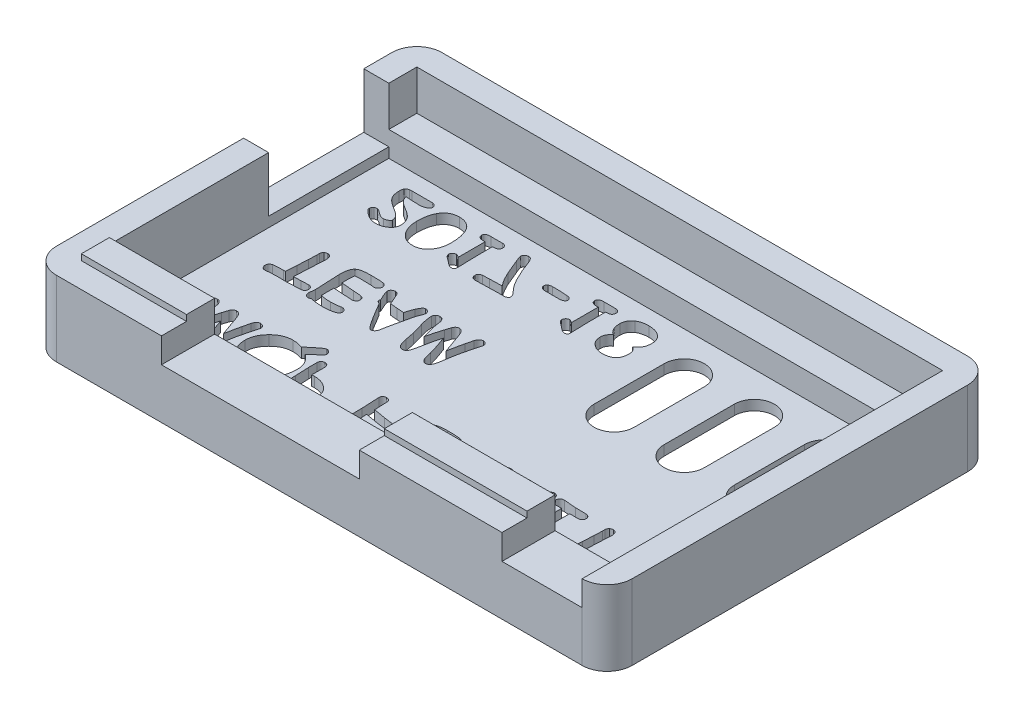
SolidWorks part; units mm, degrees
ref_plane "Front" through (0, 0, 0) normal (0, 0, 1) x (1, 0, 0)
ref_plane "Top" through (0, 0, 0) normal (0, 1, 0) x (1, 0, 0)
ref_plane "Right" through (0, 0, 0) normal (1, 0, 0) x (0, 0, -1)
sketch "Sketch1" plane through (0, 0, 0) normal (0, 1, 0) x (1, 0, 0)
  line L0 (0, 0) -> (0, 38.5)
  line L1 (0, 38.5) -> (57.5, 38.5)
  line L2 (57.5, 38.5) -> (57.5, 0)
  line L3 (57.5, 0) -> (0, 0)
  line L4 (2.5, 36) -> (2.5, 2.5)
  line L5 (2.5, 2.5) -> (55, 2.5)
  line L6 (55, 2.5) -> (55, 36)
  line L7 (55, 36) -> (2.5, 36)
  dimension "D1" = 38.5
  dimension "D2" = 57.5
  dimension "D3" = 2.5
  dimension "D4" = 2.5
  dimension "D5" = 52.5
  dimension "D6" = 33.5
extrude "Boss-Extrude1" add sketch "Sketch1" along normal blind 9
sketch "Sketch2" plane through (0, 0, 0) normal (0, 1, 0) x (1, 0, 0)
  line L1 (55, 2.5) -> (2.5, 2.5)
  line L2 (55, 2.5) -> (55, 36)
  line L3 (55, 36) -> (2.5, 36)
  line L4 (2.5, 2.5) -> (2.5, 36)
extrude "Boss-Extrude2" add sketch "Sketch2" along normal blind 2.5
sketch "Sketch3" plane through (0, 2.5, 0) normal (0, 1, 0) x (1, 0, 0)
  line L0 (2.5, 36) -> (2.5, 2.5) construction
  line L1 (55, 2.5) -> (2.5, 2.5)
  line L2 (55, 2.5) -> (55, 5.3)
  line L3 (55, 5.3) -> (2.5, 5.3)
  line L4 (2.5, 2.5) -> (2.5, 5.3)
  dimension "D1" = 2.8
extrude "Boss-Extrude3" add sketch "Sketch3" along normal blind 7.1
sketch "Sketch4" plane through (0, 0, -5.3) normal (0, 0, -1) x (-1, 0, 0)
  line L0 (-2.5, 9.6) -> (-55, 9.6) construction
  line L1 (-55, 9.6) -> (-47, 9.6)
  line L2 (-55, 9.6) -> (-55, 6.5)
  line L3 (-55, 6.5) -> (-47, 6.5)
  line L4 (-47, 9.6) -> (-47, 6.5)
  line L6 (-32.75, 9.6) -> (-13, 9.6)
  line L7 (-32.75, 9.6) -> (-32.75, 6.5)
  line L8 (-32.75, 6.5) -> (-13, 6.5)
  line L9 (-13, 9.6) -> (-13, 6.5)
  line L10 (-22.875, 9.6) -> (-22.875, 6.5) construction
  dimension "D1" = 3.1
  dimension "D2" = 3.1
  dimension "D3" = 19.75
  dimension "D4" = 8
  dimension "D5" = 14.25
sketch "Sketch5" plane through (0, 2.5, 0) normal (0, 1, 0) x (1, 0, 0)
  line L0 (55, 5.3) -> (55, 36) construction
  line L1 (2.5, 36) -> (55, 36)
  line L2 (2.5, 36) -> (2.5, 33.2)
  line L3 (2.5, 33.2) -> (55, 33.2)
  line L4 (55, 36) -> (55, 33.2)
  dimension "D1" = 2.8
extrude "Boss-Extrude4" add sketch "Sketch5" along normal blind 2.5
extrude "Cut-Extrude1" cut sketch "Sketch4" against normal up to surface (5.3 mm away) up to face at (28.75, 4.5, 0)
sketch "Sketch7" plane through (0, 0, 0) normal (-1, 0, 0) x (0, 0, 1)
  line L0 (-31.2, 9) -> (-31.2, 6) construction
  line L1 (-38.5, 9) -> (-36, 9) construction
  line L2 (-38.5, 9) -> (-38.5, 3.5) construction
  line L3 (-38.5, 3.5) -> (-36, 3.5) construction
  line L4 (-36, 9) -> (-36, 3.5) construction
  line L5 (-36, 9) -> (-33.2, 9) construction
  line L6 (-36, 9) -> (-36, 3.5) construction
  line L7 (-36, 3.5) -> (-33.2, 3.5) construction
  line L8 (-33.2, 9) -> (-33.2, 3.5)
  line L9 (-33.2, 9) -> (-21.2, 9)
  line L10 (-33.2, 9) -> (-33.2, 3.5)
  line L11 (-33.2, 3.5) -> (-21.2, 3.5)
  line L12 (-21.2, 9) -> (-21.2, 3.5)
  line L13 (-31.2, 6) -> (-23.2, 6) construction
  line L14 (-23.2, 6) -> (-23.2, 9) construction
  line M9 (0, 9) -> (-38.5, 9)
  dimension "D1" = 2.5
  dimension "D2" = 2.8
  dimension "D3" = 12
  dimension "D4" = 5.5
  dimension "D5" = 8
  dimension "D6" = 3
  dimension "D7" = 4.8
extrude "Cut-Extrude2" cut sketch "Sketch7" against normal up to surface (2.5 mm away) contours L12 L8 L11 M9 region at (0, 6.25, -27.2) up to face at (2.5, 5.5, -24.8333)
sketch "Sketch8" plane through (0, 2.5, 0) normal (0, 1, 0) x (1, 0, 0)
  line L3 (2.5, 5.3) -> (55, 5.3) construction
  line L4 (2.5, 5.3) -> (2.5, 33.2) construction
  line L5 (2.5, 33.2) -> (55, 33.2) construction
  line L6 (55, 5.3) -> (55, 33.2) construction
sketch "Sketch9" plane through (0, 0, 0) normal (0, -1, 0) x (1, 0, 0)
  line L0 (5.5, -12.3) -> (5.5, -5.3) construction
  line L1 (2.5, -5.3) -> (55, -5.3) construction
  line L2 (5.5, -12.3) -> (2.5, -12.3) construction
  line L3 (2.5, -5.3) -> (2.5, -33.2) construction
  line L4 (31, -33.2) -> (31, -18.2) construction
  line L5 (2.5, -33.2) -> (55, -33.2) construction
  line L6 (31, -18.2) -> (55, -18.2) construction
  line L7 (55, -5.3) -> (55, -33.2) construction
  line L8 (43, -18.2) -> (43, -33.2) construction
  line L9 (43, -22.2) -> (43, -29.2) construction
  line L10 (45, -22.2) -> (45, -29.2)
  line L11 (41, -22.2) -> (41, -29.2)
  line L12 (50, -22.2) -> (50, -29.2) construction
  line L13 (52, -22.2) -> (52, -29.2)
  line L14 (48, -22.2) -> (48, -29.2)
  line L15 (36, -22.2) -> (36, -29.2) construction
  line L16 (38, -22.2) -> (38, -29.2)
  line L17 (34, -22.2) -> (34, -29.2)
  arc A0 (45, -22.2) -> (41, -22.2) centre (43, -22.2) ccw
  arc A1 (41, -29.2) -> (45, -29.2) centre (43, -29.2) ccw
  arc A2 (52, -22.2) -> (48, -22.2) centre (50, -22.2) ccw
  arc A3 (48, -29.2) -> (52, -29.2) centre (50, -29.2) ccw
  arc A4 (38, -22.2) -> (34, -22.2) centre (36, -22.2) ccw
  arc A5 (34, -29.2) -> (38, -29.2) centre (36, -29.2) ccw
  text T0 "MQP HERMIT\r\nTEAM\r\n2017-18" font "Comic Sans MS" height in points 18
  point P18 (43, -25.7)
  point P26 (50, -25.7)
  point P33 (36, -25.7)
  dimension "D6" = 2
  dimension "D1" = 7
  dimension "D2" = 3
  dimension "D3" = 24
  dimension "D4" = 15
  dimension "D5" = 7
  dimension "D9" = 7
  dimension "D10" = 7
  dimension "D7" = 2
  dimension "D8" = 2
extrude "Cut-Extrude4" cut sketch "Sketch9" against normal up to next
sketch "Sketch10" plane through (0, 0, 0) normal (-1, 0, 0) x (0, 0, 1)
  line L0 (0, 9) -> (0, 0) construction
  line L1 (-38.5, 0) -> (0, 0)
  line L2 (-38.5, 0) -> (-38.5, 1.5)
  line L3 (-38.5, 1.5) -> (0, 1.5)
  line L4 (0, 0) -> (0, 1.5)
  dimension "D1" = 1.5
extrude "Cut-Extrude5" cut sketch "Sketch10" against normal up to surface (57.5 mm away) up to face at (57.5, 4.5, -19.25)
fillet "Fillet1" radius 2.5 4 edges at (57.5, 5.25, 0) (57.5, 5.25, -38.5) (0, 5.25, -38.5) (0, 5.25, 0)
